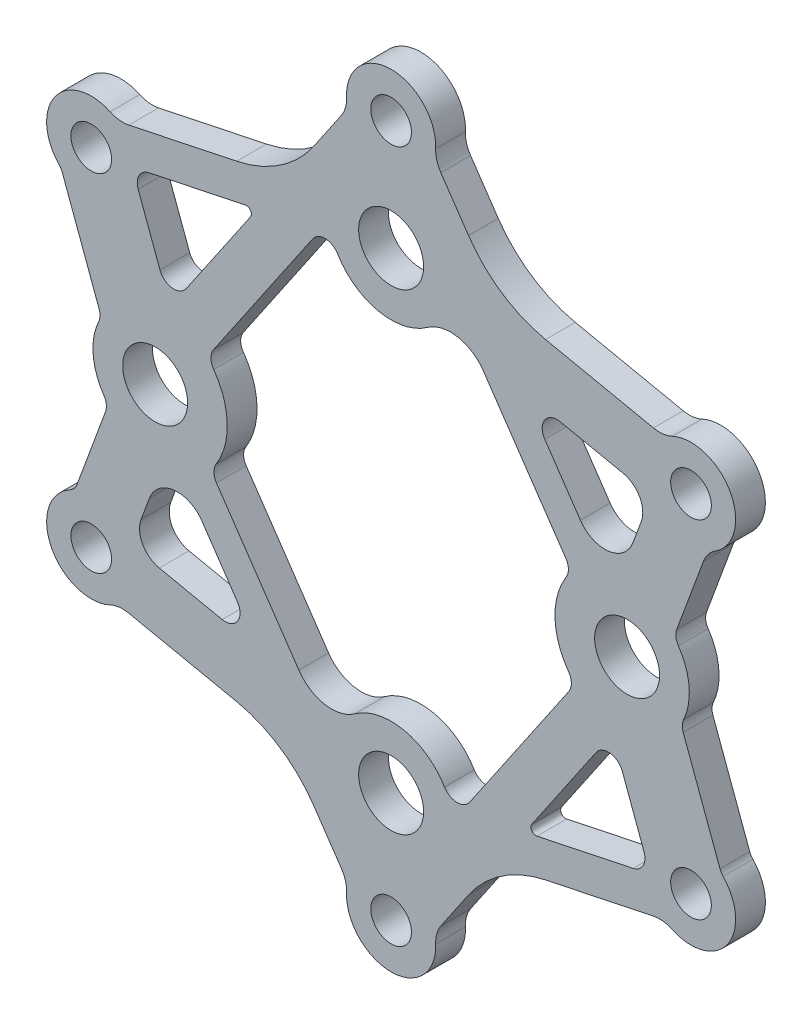
SolidWorks part; units mm, degrees
material "6061-T6 (SS)"
ref_plane "Front Plane" through (0, 0, 0) normal (0, 0, 1) x (1, 0, 0)
ref_plane "Top Plane" through (0, 0, 0) normal (0, 1, 0) x (1, 0, 0)
ref_plane "Right Plane" through (0, 0, 0) normal (1, 0, 0) x (0, 0, -1)
sketch "Sketch1" plane through (0, 0, 0) normal (1, 0, 0) x (0, 0, -1)
  line L0 (0, 60.4) -> (2, 60.4) construction
  line L1 (-42.4027, 0) -> (42.4027, 0) construction
  line L2 (2, 60.4) -> (2, 79) construction
  line L3 (2, 79) -> (6, 79)
  line L4 (6, 79) -> (6, 58.75)
  line L5 (6, 58.75) -> (11.83, 58.75) construction
  line L6 (11.83, 58.75) -> (11.83, 30.4) construction
  line L7 (0, 30.4) -> (6, 30.4)
  line L8 (0, 30.4) -> (0, 60.4)
  line L9 (0, 60.4) -> (0, 79)
  line L10 (0, 79) -> (2, 79)
  line L11 (6, 58.75) -> (6, 30.4)
  line L12 (6, 30.4) -> (11.83, 30.4) construction
  dimension "D1" = 60.4
  dimension "D2" = 4
  dimension "D3" = 6
  dimension "D4" = 158
  dimension "D5" = 58.75
  dimension "D6" = 11.83
  dimension "D7" = 60.8
revolve "Revolve1" add sketch "Sketch1" angle 360 about L1
sketch "Sketch2" plane through (0, 0, 0) normal (0, 0, 1) x (1, 0, 0)
  circle A0 centre (0, 50) radius 6
  circle A1 centre (50, 0) radius 6
  circle A2 centre (0, -50) radius 6
  circle A3 centre (-50, 0) radius 6
  point P12 (0, 0)
  dimension "D2" = 12
  dimension "D1" = 50
  dimension "D3" = 4
chamfer "Chamfer1" distance 2 angle 45 1 edges at (30.4, 0, 0)
sketch "Sketch3" plane through (0, 0, 0) normal (0, 0, 1) x (1, 0, 0)
  circle A0 centre (0, 69.85) radius 4.1021
  circle A1 centre (60.4919, 34.925) radius 4.1021
  circle A2 centre (60.4919, -34.925) radius 4.1021
  circle A3 centre (0, -69.85) radius 4.1021
  circle A4 centre (-60.4919, -34.925) radius 4.1021
  circle A5 centre (-60.4919, 34.925) radius 4.1021
  point P15 (0, 0)
  dimension "D1" = 8.2042
  dimension "D2" = 69.85
  dimension "D3" = 6
extrude "Cut-Extrude2" cut sketch "Sketch3" against normal through all
sketch "Sketch5" plane through (0, 0, 0) normal (0, 0, 1) x (1, 0, 0)
  circle A0 centre (0, 47.6) radius 6.5481
  circle A1 centre (47.6, 0) radius 6.5481
  circle A2 centre (0, -47.6) radius 6.5481
  circle A3 centre (-47.6, 0) radius 6.5481
  circle A4 centre (0, 0) radius 47.6 construction
  point P12 (0, 0)
  dimension "D1" = 13.0962
  dimension "D3" = 4
  dimension "D2" = 47.6
extrude "Cut-Extrude3" cut sketch "Sketch5" against normal through all
ref_plane "Plane1" through (0, 0, -3) normal (0, 0, 1) x (1, 0, 0)
sketch "Sketch7" plane through (0, 0, -3) normal (0, 0, 1) x (1, 0, 0)
  circle A0 centre (0, 69.85) radius 4.1021
  circle A1 centre (0, 69.85) radius 4.1021
  circle A2 centre (60.4919, 34.925) radius 4.1021
  circle A3 centre (60.4919, 34.925) radius 4.1021
  circle A4 centre (60.4919, -34.925) radius 4.1021
  circle A5 centre (60.4919, -34.925) radius 4.1021
  circle A6 centre (-60.4919, -34.925) radius 4.1021
  circle A7 centre (-60.4919, -34.925) radius 4.1021
  circle A8 centre (-60.4919, 34.925) radius 4.1021
  circle A9 centre (-60.4919, 34.925) radius 4.1021
  circle A10 centre (0, 47.6) radius 6.5481
  circle A11 centre (0, 47.6) radius 6.5481
  circle A12 centre (47.6, 0) radius 6.5481
  circle A13 centre (47.6, 0) radius 6.5481
  circle A14 centre (0, -47.6) radius 6.5481
  circle A15 centre (0, -47.6) radius 6.5481
  circle A16 centre (-47.6, 0) radius 6.5481
  circle A17 centre (-47.6, 0) radius 6.5481
  circle A18 centre (0, -69.85) radius 4.1021
  circle A19 centre (0, -69.85) radius 4.1021
extrude "Boss-ExtrudePins4FEA" [suppressed] add sketch "Sketch7" along normal blind 6 and the other way blind 6 separate body
sketch "Sketch8" [suppressed] plane through (0, 0, 0) normal (0, 0, 1) x (1, 0, 0)
  line L0 (0, 93.9117) -> (0, -93.9117) construction
  line L1 (-9, 78.4857) -> (-14.4583, 52.8065)
  line L2 (81.3299, 46.9558) -> (-81.3299, -46.9558) construction
  line L3 (-81.3299, 46.9558) -> (81.3299, -46.9558) construction
  line L4 (-63.4706, 47.0371) -> (-38.5027, 38.9245)
  line L5 (9, -78.4857) -> (14.4583, -52.8065)
  line L6 (63.4706, -47.0371) -> (38.5027, -38.9245)
  circle A2 centre (0, 0) radius 79 construction
  arc A3 (-20.1998, 45.738) -> (-29.5104, 40.3626) centre (0, 0) ccw
  arc A4 (-14.4583, 52.8065) -> (-20.1998, 45.738) centre (-24.2397, 54.8857) cw
  arc A5 (-38.5027, 38.9245) -> (-29.5104, 40.3626) centre (-35.4125, 48.4351) ccw
  arc A6 (-9, 78.4857) -> (-63.4706, 47.0371) centre (0, 0) ccw
  arc A7 (14.4583, -52.8065) -> (20.1998, -45.738) centre (24.2397, -54.8857) cw
  arc A8 (29.5104, -40.3626) -> (20.1998, -45.738) centre (0, 0) cw
  arc A9 (38.5027, -38.9245) -> (29.5104, -40.3626) centre (35.4125, -48.4351) ccw
  arc A10 (63.4706, -47.0371) -> (9, -78.4857) centre (0, 0) cw
  point P2 (60.4919, -34.925)
  dimension "D3" = 50
  dimension "D4" = 12
  dimension "D7" = 10
  dimension "D1" = 60
  dimension "D2" = 60
  dimension "D5" = 9
  dimension "D6" = 12
sketch "Sketch9" [suppressed] plane through (0, 0, 0) normal (0, 0, 1) x (1, 0, 0)
  line L0 (-10.0437, 78.3589) -> (-17.4647, 52.4788)
  line L1 (-62.839, 47.8776) -> (-36.7156, 41.3643)
  line L2 (0, 94.0842) -> (0, -94.0842) construction
  line L3 (81.4793, 47.0421) -> (-81.4793, -47.0421) construction
  line L4 (-81.4793, 47.0421) -> (81.4793, -47.0421) construction
  line L5 (10.0437, -78.3589) -> (17.4647, -52.4788)
  line L6 (62.839, -47.8776) -> (36.7156, -41.3643)
  line L7 (-72.2116, 32.0389) -> (-64.2849, 10.2606)
  line L8 (-72.2116, -32.0389) -> (-64.2849, -10.2606)
  line L9 (72.2116, -32.0389) -> (64.2849, -10.2606)
  line L10 (72.2116, 32.0389) -> (64.2849, 10.2606)
  line L11 (-9.476, -78.4296) -> (-22.2352, -46.8496)
  line L12 (-37.0696, -39.9322) -> (-62.5767, -48.2199)
  line L13 (22.2352, 46.8496) -> (9.476, 78.4296)
  line L14 (62.5767, 48.2199) -> (37.0696, 39.9322)
  circle A0 centre (0, 0) radius 79 construction
  circle A1 centre (0, 69.85) radius 4.1021 construction
  circle A2 centre (-60.4919, 34.925) radius 4.1021 construction
  arc A3 (-17.4647, 52.4788) -> (-36.7156, 41.3643) centre (-32.8449, 56.889) cw
  arc A4 (-10.0437, 78.3589) -> (-62.839, 47.8776) centre (0, 0) ccw
  arc A5 (62.839, -47.8776) -> (10.0437, -78.3589) centre (0, 0) cw
  arc A6 (36.7156, -41.3643) -> (17.4647, -52.4788) centre (32.8449, -56.889) ccw
  circle A7 centre (-60.4919, 34.925) radius 4.1021 construction
  arc A8 (72.2116, 32.0389) -> (72.2116, -32.0389) centre (0, 0) cw
  arc A9 (-64.2849, 10.2606) -> (-64.2849, -10.2606) centre (-92.4757, 0) cw
  arc A10 (-72.2116, 32.0389) -> (-72.2116, -32.0389) centre (0, 0) ccw
  arc A11 (64.2849, 10.2606) -> (64.2849, -10.2606) centre (92.4757, 0) ccw
  circle A12 centre (0, -69.85) radius 4.1021 construction
  circle A13 centre (-60.4919, -34.925) radius 4.1021 construction
  arc A14 (-22.2352, -46.8496) -> (-37.0696, -39.9322) centre (-33.3614, -51.3449) ccw
  arc A15 (-9.476, -78.4296) -> (-62.5767, -48.2199) centre (0, 0) cw
  arc A16 (62.5767, 48.2199) -> (9.476, 78.4296) centre (0, 0) ccw
  arc A17 (37.0696, 39.9322) -> (22.2352, 46.8496) centre (33.3614, 51.3449) cw
  circle A18 centre (60.4919, 34.925) radius 4.1021 construction
  point P12 (-60.4919, 34.925)
  point P13 (60.4919, 34.925)
  dimension "D3" = 12
  dimension "D4" = 16
  dimension "D5" = 16
  dimension "D6" = 40
  dimension "D2" = 12
  dimension "D8" = 12
  dimension "D10" = 30
  dimension "D11" = 12
  dimension "D12" = 12
  dimension "D14" = 12
  dimension "D15" = 12
  dimension "D16" = 22
  dimension "D17" = 12
  dimension "D18" = 12
  dimension "D19" = 12
  dimension "D1" = 16
  dimension "D7" = 40
  dimension "D9" = 12
  dimension "D13" = 22
extrude "Cut-Extrude4" [suppressed] cut sketch "Sketch9" against normal through all
fillet "Fillet1" [suppressed] radius 12
sketch "Sketch10" plane through (0, 0, 0) normal (0, 0, 1) x (1, 0, 0)
  line L0 (0, 69.85) -> (-47.6, 0) construction
  line L1 (-47.6, 0) -> (0, -69.85) construction
  line L2 (0, 0) -> (0, 84.8324) construction
  line L3 (0, 69.85) -> (47.6, 0) construction
  line L4 (0, 47.6) -> (-60.4919, 34.925) construction
  line L5 (-60.4919, 34.925) -> (-47.6, 0) construction
  line L6 (-47.6, 0) -> (-60.4919, -34.925) construction
  line L7 (-60.4919, -34.925) -> (0, -47.6) construction
  line L8 (-38.1713, -19.1633) -> (-30.9893, -29.7024)
  line L9 (0, 47.6) -> (60.4919, 34.925) construction
  line L10 (60.4919, 34.925) -> (47.6, 0) construction
  line L11 (47.6, 0) -> (60.4919, -34.925) construction
  line L12 (-10.0264, 65.7915) -> (-15.6121, 57.5948)
  line L13 (-52.9136, 42.6432) -> (-31.1443, 47.2046)
  line L16 (-52.9136, -42.6432) -> (-31.1443, -47.2046)
  line L17 (-15.6121, -57.5948) -> (-10.0264, -65.7915)
  line L18 (-48.8231, 36.3483) -> (-29.3995, 40.4181)
  line L19 (-28.3681, 38.8763) -> (-41.3419, 19.8381)
  line L20 (-46.6353, 20.4886) -> (-51.0223, 32.3732)
  line L21 (0, 0) -> (-84.0429, 0) construction
  line L22 (-34.0837, -34.3281) -> (-46.7828, -31.6672)
  line L23 (-50.448, -25.042) -> (-48.7583, -20.4644)
  line L24 (46.6353, -20.4886) -> (51.0223, -32.3732)
  line L25 (60.4919, -34.925) -> (0, -47.6) construction
  line L26 (0, -69.85) -> (47.6, 0) construction
  line L27 (48.8231, -36.3483) -> (29.3995, -40.4181)
  line L28 (28.3681, -38.8763) -> (41.3419, -19.8381)
  line L29 (34.0837, 34.3281) -> (46.7828, 31.6672)
  line L30 (50.448, 25.042) -> (48.7583, 20.4644)
  line L31 (38.1713, 19.1633) -> (30.9893, 29.7024)
  line L32 (31.1443, 47.2046) -> (52.9136, 42.6432)
  line L33 (10.0264, 65.7915) -> (15.6121, 57.5948)
  line L36 (52.9136, -42.6432) -> (31.1443, -47.2046)
  line L37 (10.0264, -65.7915) -> (15.6121, -57.5948)
  line L38 (-15.8212, 41.3061) -> (-35.8345, 11.9378)
  line L39 (66.3361, -27.6556) -> (58.9102, -7.5381)
  line L40 (-35.2329, -11.0449) -> (-18.6162, -35.4288)
  line L41 (-58.9102, 7.5381) -> (-66.3361, 27.6556)
  line L42 (15.8212, -41.3061) -> (35.8345, -11.9378)
  line L43 (-63.372, -25.4011) -> (-57.6192, -9.8163)
  line L44 (35.2329, 11.0449) -> (18.6162, 35.4288)
  line L45 (63.004, 24.4041) -> (57.6192, 9.8163)
  arc A0 (8.9908, 69.4422) -> (-8.9908, 69.4422) centre (0, 69.85) ccw
  arc A1 (-56.6832, 43.0794) -> (-66.9859, 28.6938) centre (-60.4919, 34.925) ccw
  arc A2 (-64.7628, -27.0029) -> (-56.6832, -43.0794) centre (-60.4919, -34.925) ccw
  arc A3 (8.9908, -69.4422) -> (-8.9908, -69.4422) centre (0, -69.85) cw
  arc A4 (-41.3419, 19.8381) -> (-46.6353, 20.4886) centre (-43.821, 21.5275) cw
  arc A5 (-29.3995, 40.4181) -> (-28.3681, 38.8763) centre (-29.1945, 39.4394) cw
  arc A6 (-48.8231, 36.3483) -> (-51.0223, 32.3732) centre (-48.2079, 33.412) ccw
  arc A7 (-46.7828, -31.6672) -> (-50.448, -25.042) centre (-45.7574, -26.7735) cw
  arc A8 (-30.9893, -29.7024) -> (-34.0837, -34.3281) centre (-33.4684, -31.3918) cw
  arc A9 (-38.1713, -19.1633) -> (-48.7583, -20.4644) centre (-43.1295, -22.5421) ccw
  arc A10 (-31.1443, -47.2046) -> (-15.6121, -57.5948) centre (-36.2713, -71.6732) cw
  arc A12 (-15.6121, 57.5948) -> (-31.1443, 47.2046) centre (-36.2713, 71.6732) cw
  arc A13 (48.7583, 20.4644) -> (38.1713, 19.1633) centre (43.1295, 22.5421) cw
  arc A14 (46.7828, 31.6672) -> (50.448, 25.042) centre (45.7574, 26.7735) cw
  arc A15 (34.0837, 34.3281) -> (30.9893, 29.7024) centre (33.4684, 31.3918) ccw
  arc A16 (29.3995, -40.4181) -> (28.3681, -38.8763) centre (29.1945, -39.4394) cw
  arc A17 (51.0223, -32.3732) -> (48.8231, -36.3483) centre (48.2079, -33.412) cw
  arc A18 (46.6353, -20.4886) -> (41.3419, -19.8381) centre (43.821, -21.5275) ccw
  arc A19 (56.6832, 43.0794) -> (65.3764, 27.3658) centre (60.4919, 34.925) cw
  arc A20 (66.9859, -28.6938) -> (56.6832, -43.0794) centre (60.4919, -34.925) cw
  arc A21 (31.1443, -47.2046) -> (15.6121, -57.5948) centre (36.2713, -71.6732) ccw
  arc A23 (31.1443, 47.2046) -> (15.6121, 57.5948) centre (36.2713, 71.6732) cw
  arc A24 (-8.9908, 69.4422) -> (-10.0264, 65.7915) centre (-14.9846, 69.1703) cw
  arc A25 (56.6832, 43.0794) -> (52.9136, 42.6432) centre (54.1441, 48.5157) cw
  arc A26 (65.3764, 27.3658) -> (63.004, 24.4041) centre (68.6328, 22.3264) ccw
  arc A27 (56.6832, -43.0794) -> (52.9136, -42.6432) centre (54.1441, -48.5157) ccw
  arc A28 (8.9908, -69.4422) -> (10.0264, -65.7915) centre (14.9846, -69.1703) cw
  arc A29 (-56.6832, -43.0794) -> (-52.9136, -42.6432) centre (-54.1441, -48.5157) cw
  arc A31 (-56.6832, 43.0794) -> (-52.9136, 42.6432) centre (-54.1441, 48.5157) ccw
  arc A32 (10.0264, 65.7915) -> (8.9908, 69.4422) centre (14.9846, 69.1703) cw
  arc A33 (-8.9908, -69.4422) -> (-10.0264, -65.7915) centre (-14.9846, -69.1703) ccw
  arc A34 (-35.7907, 8.4963) -> (-35.2918, -7.7561) centre (-47.6, 0) cw
  arc A35 (35.2918, 7.7561) -> (35.7907, -8.4963) centre (47.6, 0) ccw
  circle A36 centre (-47.6, 0) radius 6.5481 construction
  arc A37 (7.3313, 37.4163) -> (-10.7677, 41.1571) centre (0, 47.6) cw
  circle A38 centre (0, 47.6) radius 6.5481 construction
  arc A39 (10.7677, -41.1571) -> (-7.3313, -37.4163) centre (0, -47.6) ccw
  arc A40 (35.7907, -8.4963) -> (35.8345, -11.9378) centre (33.3554, -10.2484) cw
  arc A41 (35.2918, 7.7561) -> (35.2329, 11.0449) centre (32.7538, 9.3555) ccw
  arc A42 (-35.8345, 11.9378) -> (-35.7907, 8.4963) centre (-33.3554, 10.2484) ccw
  arc A43 (-35.2918, -7.7561) -> (-35.2329, -11.0449) centre (-32.7538, -9.3555) ccw
  arc A44 (10.7677, -41.1571) -> (15.8212, -41.3061) centre (13.3421, -39.6167) ccw
  arc A45 (-18.6162, -35.4288) -> (-7.3313, -37.4163) centre (-12.0053, -30.9237) ccw
  arc A46 (7.3313, 37.4163) -> (18.6162, 35.4288) centre (12.0053, 30.9237) cw
  arc A47 (-10.7677, 41.1571) -> (-15.8212, 41.3061) centre (-13.3421, 39.6167) ccw
  arc A48 (-64.7628, -27.0029) -> (-63.372, -25.4011) centre (-66.1864, -24.3622) ccw
  arc A49 (-58.9992, 5.2452) -> (-57.9574, -7.0838) centre (-47.6, 0) ccw
  arc A50 (58.9992, -5.2452) -> (57.9574, 7.0838) centre (47.6, 0) ccw
  arc A52 (-57.9574, -7.0838) -> (-57.6192, -9.8163) centre (-60.4336, -8.7774) cw
  arc A53 (-58.9102, 7.5381) -> (-58.9992, 5.2452) centre (-61.7246, 6.4993) cw
  arc A54 (66.9859, -28.6938) -> (66.3361, -27.6556) centre (69.1505, -26.6167) cw
  arc A55 (58.9102, -7.5381) -> (58.9992, -5.2452) centre (61.7246, -6.4993) cw
  arc A56 (57.9574, 7.0838) -> (57.6192, 9.8163) centre (60.4336, 8.7774) cw
  arc A57 (-66.3361, 27.6556) -> (-66.9859, 28.6938) centre (-69.1505, 26.6167) ccw
  point P55 (-58.4527, 6.2988)
  point P143 (-58.4527, 6.2988)
  dimension "D1" = 9
  dimension "D5" = 3
  dimension "D6" = 25
  dimension "D10" = 5
  dimension "D17" = 6
  dimension "D18" = 1
  dimension "D19" = 25
  dimension "D23" = 6
  dimension "D24" = 3
  dimension "D25" = 6
  dimension "D31" = 1
  dimension "D32" = 3
  dimension "D33" = 6
  dimension "D35" = 6
  dimension "D40" = 8
  dimension "D41" = 6
  dimension "D42" = 3
  dimension "D43" = 8
  dimension "D44" = 6
  dimension "D22" = 3
  dimension "D46" = 3
  dimension "D47" = 25
  dimension "D48" = 25
  dimension "D52" = 3
  dimension "D53" = 3
  dimension "D54" = 3
  dimension "D2" = 1
  dimension "D3" = 8
  dimension "D4" = 6
  dimension "D7" = 6
  dimension "D8" = 3
  dimension "D9" = 6
  dimension "D11" = 6
  dimension "D12" = 8
  dimension "D13" = 1
  dimension "D14" = 6
  dimension "D15" = 6
  dimension "D16" = 3
  dimension "D20" = 6
  dimension "D21" = 6
  dimension "D26" = 6
  dimension "D27" = 6
  dimension "D28" = 6
  dimension "D29" = 6
  dimension "D30" = 6
  dimension "D34" = 6
  dimension "D36" = 3
  dimension "D37" = 4
  dimension "D38" = 3
  dimension "D39" = 4
  dimension "D45" = 6
  dimension "D49" = 8
  dimension "D50" = 8
extrude "Cut-ExtrudeLightenSpider" cut sketch "Sketch10" against normal through all flip side to cut
sketch "Sketch11" plane through (0, 0, 0) normal (0, 0, 1) x (1, 0, 0)
  circle A0 centre (0, 0) radius 38
  dimension "D1" = 76
extrude "Cut-ExtrudeEnlargeCtrHole" [suppressed] cut sketch "Sketch11" against normal through all
ref_axis "Axis1" [suppressed] through (0, 0, 0) along (0, 0, 1)
sketch "Sketch12" plane through (0, 0, 0) normal (0, 0, 1) x (1, 0, 0)
  line L1 (-77.8089, 88.85) -> (77.8089, 88.85)
  line L2 (-77.8089, 88.85) -> (-77.8089, -88.85)
  line L3 (-77.8089, -88.85) -> (77.8089, -88.85)
  line L4 (77.8089, 88.85) -> (77.8089, -88.85)
  line L5 (-77.8089, 88.85) -> (77.8089, -88.85) construction
  line L6 (-77.8089, -88.85) -> (77.8089, 88.85) construction
  circle A0 centre (0, 0) radius 33.0519 construction
  arc A1 (35.2918, 7.7561) -> (35.7907, -8.4963) centre (47.6, 0) ccw construction
  arc A3 (-56.6832, 43.0794) -> (-66.9859, 28.6938) centre (-60.4919, 34.925) ccw construction
  arc A4 (8.9908, 69.4422) -> (-8.9908, 69.4422) centre (0, 69.85) ccw construction
  point P10 (0, 78.85)
  point P13 (-67.8089, 40.1653)
  dimension "D1" = 66.1038
  dimension "D2" = 10
  dimension "D3" = 10
extrude "Boss-Extrude1" [suppressed] add sketch "Sketch12" against normal blind 6.35
